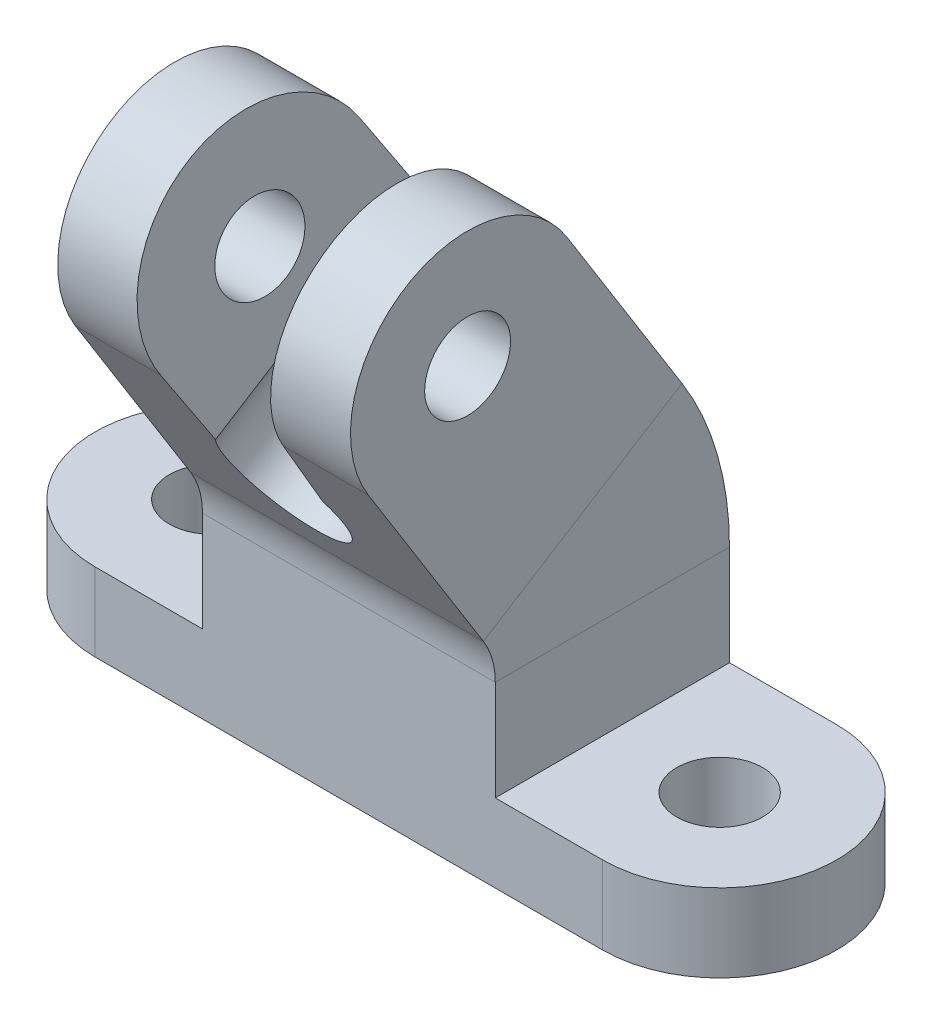
SolidWorks part; units mm, degrees
ref_plane "前视基准面" through (0, 0, 0) normal (0, 0, 1) x (1, 0, 0)
ref_plane "上视基准面" through (0, 0, 0) normal (0, 1, 0) x (1, 0, 0)
ref_plane "右视基准面" through (0, 0, 0) normal (1, 0, 0) x (0, 0, -1)
sketch "草图1" plane through (0, 0, 0) normal (0, 1, 0) x (1, 0, 0)
  line L0 (-6.5, 0) -> (6.5, 0) construction
  line L1 (-6.5, 3) -> (6.5, 3)
  line L2 (-6.5, -3) -> (6.5, -3)
  arc A0 (-6.5, 3) -> (-6.5, -3) centre (-6.5, 0) ccw
  arc A1 (6.5, -3) -> (6.5, 3) centre (6.5, 0) ccw
  point P2 (0, 0)
  dimension "D1" = 6
  dimension "D2" = 13
extrude "凸台-拉伸1" add sketch "草图1" along normal blind 2
sketch "草图7" plane through (0, 2, 0) normal (0, 1, 0) x (1, 0, 0)
  circle A0 centre (6.5, 0) radius 1.1
  circle A1 centre (-6.5, 0) radius 1.1
  dimension "D1" = 2.2
  dimension "D2" = 2.2
extrude "切除-拉伸5" cut sketch "草图7" against normal blind 3.5
sketch "草图8" plane through (0, 2, 0) normal (0, 1, 0) x (1, 0, 0)
  line L6 (3.75, 3) -> (-3.75, 3)
  line L7 (3.75, 3) -> (3.75, -3)
  line L8 (3.75, -3) -> (-3.75, -3)
  line L9 (-3.75, 3) -> (-3.75, -3)
  line L10 (3.75, 3) -> (-3.75, -3) construction
  line L11 (3.75, -3) -> (-3.75, 3) construction
  point P0 (0, 0)
  dimension "D1" = 6
  dimension "D2" = 7.5
sketch "草图9" plane through (0, 0, 0) normal (1, 0, 0) x (0, 0, -1)
  line L0 (0, 2) -> (0, 4.5663)
  line L1 (-3, 2) -> (3, 2) construction
  line L2 (-0.7598, 7.2159) -> (-5.2992, 14.4805)
  arc A0 (-0.7598, 7.2159) -> (0, 4.5663) centre (-5, 4.5663) cw
  point P8 (0, 6)
  dimension "D4" = 5
  dimension "D1" = 32
  dimension "D2" = 4
  dimension "D3" = 10
sweep "扫描1" add profiles "草图8" path "草图9"
fillet "圆角1" 2 edges at (0, 16.0702, 2.755) (0, 12.8907, 7.8433) type full round first side face at (0, 12.4379, 0.4853) second side face at (0, 9.2584, 5.5736) middle face at (0, 14.4805, 5.2992)
sketch "草图10" plane through (0, 0.0951, -0.1522) normal (0, -0.5299, 0.848) x (1, 0, 0)
  line L0 (0, 15.0883) -> (0, 9.0883) construction
  line L1 (3.75, 15.0883) -> (-3.75, 15.0883) construction
  line L2 (-1.3724, 9.8087) -> (-2.0698, 17.7803)
  line L3 (-2.0698, 17.7803) -> (2.0698, 17.7803)
  line L4 (1.3724, 9.8087) -> (2.0698, 17.7803)
  circle A0 centre (0, 9.0883) radius 1.55
  point P10 (0, 17.7803)
  line M4 (3.75, 12.0883) -> (-3.75, 12.0883)
  dimension "D1" = 3.1
  dimension "D2" = 6
  dimension "D3" = 5
extrude "切除-拉伸6" cut sketch "草图10" against normal blind 10 contours A0 | L0 A0 L4 M4 | L0 L2 A0 M4 | L4 L3 L2 M4 region at (0.8002, 9.625, 5.8027) region at (-0.7859, 10.4063, 6.2909) region at (-0.8002, 9.625, 5.8027) region at (0.7791, 8.8956, 5.3469)
sketch "草图12" plane through (-3.75, 0, 0) normal (-1, 0, 0) x (0, 0, 1)
  circle A0 centre (3.7094, 11.9363) radius 1.1
  dimension "D1" = 2.2
extrude "切除-拉伸7" cut sketch "草图12" against normal blind 10
